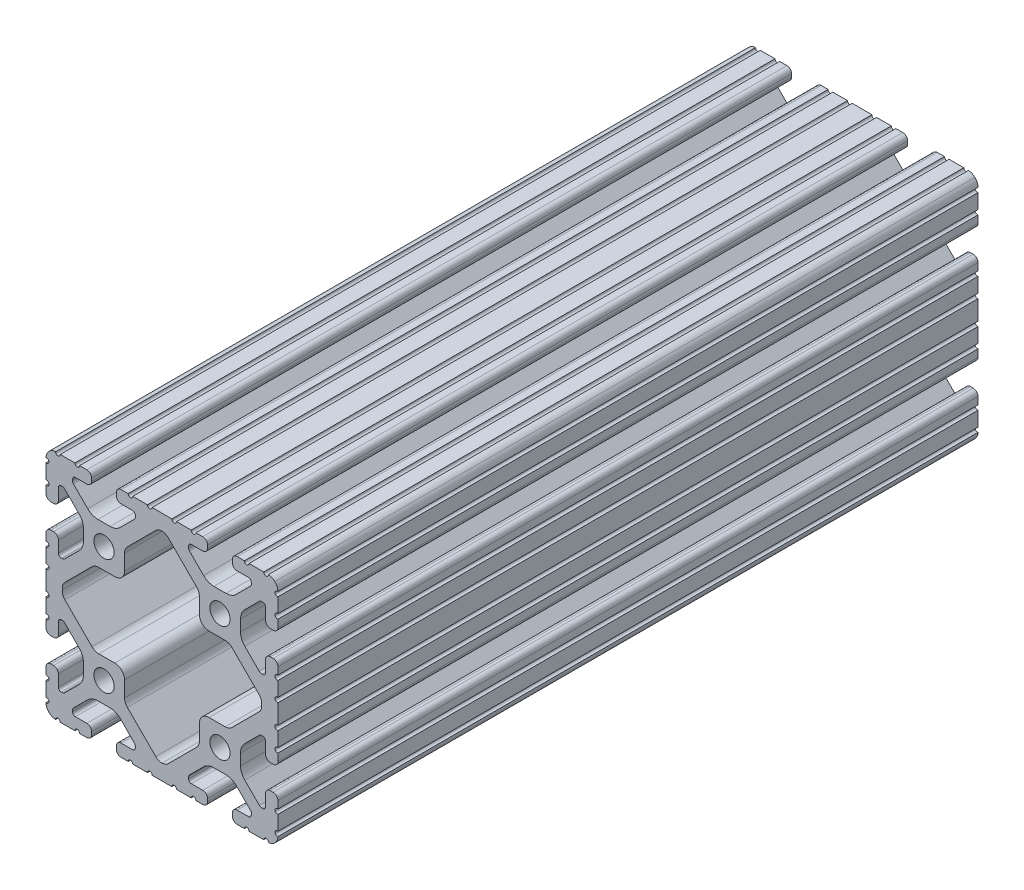
SolidWorks part; units mm, degrees
ref_plane "Front Plane" through (0, 0, 0) normal (0, 0, 1) x (1, 0, 0)
ref_plane "Top Plane" through (0, 0, 0) normal (0, 1, 0) x (1, 0, 0)
ref_plane "Right Plane" through (0, 0, 0) normal (1, 0, 0) x (0, 0, -1)
sketch "Sketch1" plane through (0, 0, 0) normal (0, 0, 1) x (1, 0, 0)
  line L0 (0, 38.1) -> (0, -38.1) construction
  line L1 (-38.1, -38.1) -> (38.1, -38.1) construction
  line L2 (-38.1, -38.1) -> (-38.1, 38.1) construction
  line L3 (-38.1, 38.1) -> (38.1, 38.1) construction
  line L4 (38.1, -38.1) -> (38.1, 38.1) construction
  line L5 (0, 38.1) -> (0, -38.1) construction
  line L6 (-38.1, 0) -> (38.1, 0) construction
  line L7 (-19.05, 19.05) -> (19.05, 19.05) construction
  line L8 (-19.05, 19.05) -> (-19.05, -19.05) construction
  line L9 (-19.05, -19.05) -> (19.05, -19.05) construction
  line L10 (19.05, 19.05) -> (19.05, -19.05) construction
  line L11 (-23.114, 38.1) -> (-23.114, -38.1) construction
  line L12 (-23.114, -38.1) -> (-14.986, 38.1) construction
  line L13 (-14.986, 38.1) -> (-14.986, -38.1) construction
  circle A0 centre (19.05, 19.05) radius 3.3274
  point P0 (0, 0)
  point P9 (0, 0)
  point P12 (-19.05, 0)
  line B0 (-11.3637, -22.8433) -> (-2.0515, -32.1555)
  line B1 (-12.2936, -15.4686) -> (-12.2936, -20.5983)
  line B2 (-20.769, -12.2936) -> (-15.4686, -12.2936)
  line B3 (-31.9021, -2.4756) -> (-23.0141, -11.3637)
  line B4 (-23.0141, 11.3637) -> (-31.9021, 2.4756)
  line B5 (-15.4686, 12.2936) -> (-20.769, 12.2936)
  line B6 (-12.2936, 20.5983) -> (-12.2936, 15.4686)
  line B7 (-2.0515, 32.1555) -> (-11.3637, 22.8433)
  line B8 (11.3637, 22.8433) -> (2.0515, 32.1555)
  line B9 (12.2936, 15.4686) -> (12.2936, 20.5983)
  line B10 (20.769, 12.2936) -> (15.4686, 12.2936)
  line B11 (31.9021, 2.4756) -> (23.0141, 11.3637)
  line B12 (23.0141, -11.3637) -> (31.9021, -2.4756)
  line B13 (15.4686, -12.2936) -> (20.769, -12.2936)
  line B14 (12.2936, -20.5983) -> (12.2936, -15.4686)
  line B15 (2.0515, -32.1555) -> (11.3637, -22.8433)
  line B16 (-4.7773, 38.1) -> (-9.6053, 38.1)
  line B17 (-11.1289, 38.1) -> (-13.4112, 38.1)
  line B18 (-14.986, 36.5252) -> (-14.986, 35.6108)
  line B19 (-13.4112, 34.036) -> (-9.652, 34.036)
  line B20 (-8.763, 33.147) -> (-8.763, 32.4935)
  line B21 (-9.0234, 31.8649) -> (-13.6907, 27.1976)
  line B22 (-17.0493, 25.8064) -> (-21.0507, 25.8064)
  line B23 (-24.4093, 27.1976) -> (-29.1002, 31.8885)
  line B24 (-29.337, 32.7207) -> (-29.337, 33.147)
  line B25 (-28.448, 34.036) -> (-24.6888, 34.036)
  line B26 (-23.114, 35.6108) -> (-23.114, 36.5252)
  line B27 (-24.6888, 38.1) -> (-27.0772, 38.1)
  line B28 (-28.6011, 38.1) -> (-33.4288, 38.1)
  line B29 (-38.1, 33.373) -> (-38.1, 28.5453)
  line B30 (-38.1, 27.0238) -> (-38.1, 24.6302)
  line B31 (-36.5252, 23.0554) -> (-35.6108, 23.0554)
  line B32 (-34.036, 24.6302) -> (-34.036, 28.448)
  line B33 (-33.147, 29.337) -> (-32.6643, 29.337)
  line B34 (-32.0357, 29.0766) -> (-27.1976, 24.2385)
  line B35 (-25.8064, 20.8799) -> (-25.8064, 17.2201)
  line B36 (-27.1976, 13.8615) -> (-31.9489, 9.1101)
  line B37 (-32.7869, 8.763) -> (-33.0603, 8.763)
  line B38 (-34.036, 9.7387) -> (-34.036, 13.4698)
  line B39 (-35.6108, 15.0446) -> (-36.5252, 15.0446)
  line B40 (-38.1, 13.4698) -> (-38.1, 11.075)
  line B41 (-38.1, 9.552) -> (-38.1, 4.7238)
  line B42 (-38.1, 3.2007) -> (-38.1, -3.2007)
  line B43 (-38.1, -4.7238) -> (-38.1, -9.552)
  line B44 (-38.1, -11.075) -> (-38.1, -13.4698)
  line B45 (-36.5252, -15.0446) -> (-35.6108, -15.0446)
  line B46 (-34.036, -13.4698) -> (-34.036, -9.7387)
  line B47 (-33.0603, -8.763) -> (-32.7869, -8.763)
  line B48 (-31.9489, -9.1101) -> (-27.1976, -13.8615)
  line B49 (-25.8064, -17.2201) -> (-25.8064, -20.8799)
  line B50 (-27.1976, -24.2385) -> (-32.0357, -29.0766)
  line B51 (-32.6643, -29.337) -> (-33.147, -29.337)
  line B52 (-34.036, -28.448) -> (-34.036, -24.6302)
  line B53 (-35.6108, -23.0554) -> (-36.5252, -23.0554)
  line B54 (-38.1, -24.6302) -> (-38.1, -27.0238)
  line B55 (-38.1, -28.5453) -> (-38.1, -33.373)
  line B56 (-33.4288, -38.1) -> (-28.6011, -38.1)
  line B57 (-27.0772, -38.1) -> (-24.6888, -38.1)
  line B58 (-23.114, -36.5252) -> (-23.114, -35.6108)
  line B59 (-24.6888, -34.036) -> (-28.448, -34.036)
  line B60 (-29.337, -33.147) -> (-29.337, -32.7207)
  line B61 (-29.1002, -31.8885) -> (-24.4093, -27.1976)
  line B62 (-21.0507, -25.8064) -> (-17.0493, -25.8064)
  line B63 (-13.6907, -27.1976) -> (-9.0234, -31.8649)
  line B64 (-8.763, -32.4935) -> (-8.763, -33.147)
  line B65 (-9.652, -34.036) -> (-13.4112, -34.036)
  line B66 (-14.986, -35.6108) -> (-14.986, -36.5252)
  line B67 (-13.4112, -38.1) -> (-11.1289, -38.1)
  line B68 (-9.6053, -38.1) -> (-4.7773, -38.1)
  line B69 (-3.2537, -38.1) -> (3.2537, -38.1)
  line B70 (4.7773, -38.1) -> (9.6053, -38.1)
  line B71 (11.1289, -38.1) -> (13.4112, -38.1)
  line B72 (14.986, -36.5252) -> (14.986, -35.6108)
  line B73 (13.4112, -34.036) -> (9.652, -34.036)
  line B74 (8.763, -33.147) -> (8.763, -32.4935)
  line B75 (9.0234, -31.8649) -> (13.6907, -27.1976)
  line B76 (17.0493, -25.8064) -> (21.0507, -25.8064)
  line B77 (24.4093, -27.1976) -> (29.1002, -31.8885)
  line B78 (29.337, -32.7207) -> (29.337, -33.147)
  line B79 (28.448, -34.036) -> (24.6888, -34.036)
  line B80 (23.114, -35.6108) -> (23.114, -36.5252)
  line B81 (24.6888, -38.1) -> (27.0772, -38.1)
  line B82 (28.6011, -38.1) -> (33.4288, -38.1)
  line B83 (38.1, -33.373) -> (38.1, -28.5453)
  line B84 (38.1, -27.0238) -> (38.1, -24.6302)
  line B85 (36.5252, -23.0554) -> (35.6108, -23.0554)
  line B86 (34.036, -24.6302) -> (34.036, -28.448)
  line B87 (33.147, -29.337) -> (32.6643, -29.337)
  line B88 (32.0357, -29.0766) -> (27.1976, -24.2385)
  line B89 (25.8064, -20.8799) -> (25.8064, -17.2201)
  line B90 (27.1976, -13.8615) -> (31.9489, -9.1101)
  line B91 (32.7869, -8.763) -> (33.0603, -8.763)
  line B92 (34.036, -9.7387) -> (34.036, -13.4698)
  line B93 (35.6108, -15.0446) -> (36.5252, -15.0446)
  line B94 (38.1, -13.4698) -> (38.1, -11.075)
  line B95 (38.1, -9.552) -> (38.1, -4.7238)
  line B96 (38.1, -3.2007) -> (38.1, 3.2007)
  line B97 (38.1, 4.7238) -> (38.1, 9.552)
  line B98 (38.1, 11.075) -> (38.1, 13.4698)
  line B99 (36.5252, 15.0446) -> (35.6108, 15.0446)
  line B100 (34.036, 13.4698) -> (34.036, 9.7387)
  line B101 (33.0603, 8.763) -> (32.7869, 8.763)
  line B102 (31.9489, 9.1101) -> (27.1976, 13.8615)
  line B103 (25.8064, 17.2201) -> (25.8064, 20.8799)
  line B104 (27.1976, 24.2385) -> (32.0357, 29.0766)
  line B105 (32.6643, 29.337) -> (33.147, 29.337)
  line B106 (34.036, 28.448) -> (34.036, 24.6302)
  line B107 (35.6108, 23.0554) -> (36.5252, 23.0554)
  line B108 (38.1, 24.6302) -> (38.1, 27.0238)
  line B109 (38.1, 28.5453) -> (38.1, 33.373)
  line B110 (33.4288, 38.1) -> (28.6011, 38.1)
  line B111 (27.0772, 38.1) -> (24.6888, 38.1)
  line B112 (23.114, 36.5252) -> (23.114, 35.6108)
  line B113 (24.6888, 34.036) -> (28.448, 34.036)
  line B114 (29.337, 33.147) -> (29.337, 32.7207)
  line B115 (29.1002, 31.8885) -> (24.4093, 27.1976)
  line B116 (21.0507, 25.8064) -> (17.0493, 25.8064)
  line B117 (13.6907, 27.1976) -> (9.0234, 31.8649)
  line B118 (8.763, 32.4935) -> (8.763, 33.147)
  line B119 (9.652, 34.036) -> (13.4112, 34.036)
  line B120 (14.986, 35.6108) -> (14.986, 36.5252)
  line B121 (13.4112, 38.1) -> (11.1289, 38.1)
  line B122 (9.6053, 38.1) -> (4.7773, 38.1)
  line B123 (3.2537, 38.1) -> (-3.2537, 38.1)
  circle B124 centre (-19.05, 19.05) radius 3.3274
  circle B125 centre (-19.05, -19.05) radius 3.3274
  circle B126 centre (19.05, -19.05) radius 3.3274
  circle B127 centre (19.05, 19.05) radius 3.3274
  arc B128 (0, -33.011) -> (2.0515, -32.1555) centre (-0.0139, -30.09) ccw
  arc B129 (-2.0515, -32.1555) -> (0, -33.011) centre (0.0139, -30.09) ccw
  arc B130 (-12.2936, -20.5983) -> (-11.3637, -22.8433) centre (-9.1186, -20.5983) ccw
  arc B131 (-12.2936, -15.4686) -> (-15.4686, -12.2936) centre (-15.4686, -15.4686) ccw
  arc B132 (-23.0141, -11.3637) -> (-20.769, -12.2936) centre (-20.769, -9.1186) ccw
  arc B133 (-32.7287, 0) -> (-31.9021, -2.4756) centre (-29.8367, -0.4102) ccw
  arc B134 (-31.9021, 2.4756) -> (-32.7287, 0) centre (-29.8367, 0.4102) ccw
  arc B135 (-20.769, 12.2936) -> (-23.0141, 11.3637) centre (-20.769, 9.1186) ccw
  arc B136 (-15.4686, 12.2936) -> (-12.2936, 15.4686) centre (-15.4686, 15.4686) ccw
  arc B137 (-11.3637, 22.8433) -> (-12.2936, 20.5983) centre (-9.1186, 20.5983) ccw
  arc B138 (0, 33.011) -> (-2.0515, 32.1555) centre (0.0139, 30.09) ccw
  arc B139 (2.0515, 32.1555) -> (0, 33.011) centre (-0.0139, 30.09) ccw
  arc B140 (12.2936, 20.5983) -> (11.3637, 22.8433) centre (9.1186, 20.5983) ccw
  arc B141 (12.2936, 15.4686) -> (15.4686, 12.2936) centre (15.4686, 15.4686) ccw
  arc B142 (23.0141, 11.3637) -> (20.769, 12.2936) centre (20.769, 9.1186) ccw
  arc B143 (32.7287, 0) -> (31.9021, 2.4756) centre (29.8367, 0.4102) ccw
  arc B144 (31.9021, -2.4756) -> (32.7287, 0) centre (29.8367, -0.4102) ccw
  arc B145 (20.769, -12.2936) -> (23.0141, -11.3637) centre (20.769, -9.1186) ccw
  arc B146 (15.4686, -12.2936) -> (12.2936, -15.4686) centre (15.4686, -15.4686) ccw
  arc B147 (11.3637, -22.8433) -> (12.2936, -20.5983) centre (9.1186, -20.5983) ccw
  arc B148 (-4.7773, 38.1) -> (-3.2537, 38.1) centre (-4.0155, 38.0824) ccw
  arc B149 (-11.1289, 38.1) -> (-9.6053, 38.1) centre (-10.3671, 38.0824) ccw
  arc B150 (-13.4112, 38.1) -> (-14.986, 36.5252) centre (-13.4112, 36.5252) ccw
  arc B151 (-14.986, 35.6108) -> (-13.4112, 34.036) centre (-13.4112, 35.6108) ccw
  arc B152 (-8.763, 33.147) -> (-9.652, 34.036) centre (-9.652, 33.147) ccw
  arc B153 (-9.0234, 31.8649) -> (-8.763, 32.4935) centre (-9.652, 32.4935) ccw
  arc B154 (-17.0493, 25.8064) -> (-13.6907, 27.1976) centre (-17.0493, 30.5562) ccw
  arc B155 (-24.4093, 27.1976) -> (-21.0507, 25.8064) centre (-21.0507, 30.5562) ccw
  arc B156 (-29.337, 32.7207) -> (-29.1002, 31.8885) centre (-28.4716, 32.5172) ccw
  arc B157 (-28.448, 34.036) -> (-29.337, 33.147) centre (-28.448, 33.147) ccw
  arc B158 (-24.6888, 34.036) -> (-23.114, 35.6108) centre (-24.6888, 35.6108) ccw
  arc B159 (-23.114, 36.5252) -> (-24.6888, 38.1) centre (-24.6888, 36.5252) ccw
  arc B160 (-28.6011, 38.1) -> (-27.0772, 38.1) centre (-27.8392, 38.0824) ccw
  arc B161 (-34.9527, 38.1) -> (-33.4288, 38.1) centre (-34.1907, 38.0824) ccw
  arc B162 (-34.9527, 38.1) -> (-37.0861, 37.1826) centre (-34.8521, 34.9266) ccw
  arc B163 (-37.0861, 37.1826) -> (-38.1, 34.8455) centre (-34.925, 34.8566) ccw
  arc B164 (-38.1, 33.373) -> (-38.1, 34.8455) centre (-37.9035, 34.1092) ccw
  arc B165 (-38.1, 27.0238) -> (-38.1, 28.5453) centre (-37.9035, 27.7845) ccw
  arc B166 (-38.1, 24.6302) -> (-36.5252, 23.0554) centre (-36.5252, 24.6302) ccw
  arc B167 (-35.6108, 23.0554) -> (-34.036, 24.6302) centre (-35.6108, 24.6302) ccw
  arc B168 (-33.147, 29.337) -> (-34.036, 28.448) centre (-33.147, 28.448) ccw
  arc B169 (-32.0357, 29.0766) -> (-32.6643, 29.337) centre (-32.6643, 28.448) ccw
  arc B170 (-25.8064, 20.8799) -> (-27.1976, 24.2385) centre (-30.5562, 20.8799) ccw
  arc B171 (-27.1976, 13.8615) -> (-25.8064, 17.2201) centre (-30.5562, 17.2201) ccw
  arc B172 (-32.7869, 8.763) -> (-31.9489, 9.1101) centre (-32.7869, 9.9481) ccw
  arc B173 (-34.036, 9.7387) -> (-33.0603, 8.763) centre (-33.0603, 9.7387) ccw
  arc B174 (-34.036, 13.4698) -> (-35.6108, 15.0446) centre (-35.6108, 13.4698) ccw
  arc B175 (-36.5252, 15.0446) -> (-38.1, 13.4698) centre (-36.5252, 13.4698) ccw
  arc B176 (-38.1, 9.552) -> (-38.1, 11.075) centre (-37.9035, 10.3135) ccw
  arc B177 (-38.1, 3.2007) -> (-38.1, 4.7238) centre (-37.9035, 3.9622) ccw
  arc B178 (-38.1, -4.7238) -> (-38.1, -3.2007) centre (-37.9035, -3.9622) ccw
  arc B179 (-38.1, -11.075) -> (-38.1, -9.552) centre (-37.9035, -10.3135) ccw
  arc B180 (-38.1, -13.4698) -> (-36.5252, -15.0446) centre (-36.5252, -13.4698) ccw
  arc B181 (-35.6108, -15.0446) -> (-34.036, -13.4698) centre (-35.6108, -13.4698) ccw
  arc B182 (-33.0603, -8.763) -> (-34.036, -9.7387) centre (-33.0603, -9.7387) ccw
  arc B183 (-31.9489, -9.1101) -> (-32.7869, -8.763) centre (-32.7869, -9.9481) ccw
  arc B184 (-25.8064, -17.2201) -> (-27.1976, -13.8615) centre (-30.5562, -17.2201) ccw
  arc B185 (-27.1976, -24.2385) -> (-25.8064, -20.8799) centre (-30.5562, -20.8799) ccw
  arc B186 (-32.6643, -29.337) -> (-32.0357, -29.0766) centre (-32.6643, -28.448) ccw
  arc B187 (-34.036, -28.448) -> (-33.147, -29.337) centre (-33.147, -28.448) ccw
  arc B188 (-34.036, -24.6302) -> (-35.6108, -23.0554) centre (-35.6108, -24.6302) ccw
  arc B189 (-36.5252, -23.0554) -> (-38.1, -24.6302) centre (-36.5252, -24.6302) ccw
  arc B190 (-38.1, -28.5453) -> (-38.1, -27.0238) centre (-37.9035, -27.7845) ccw
  arc B191 (-38.1, -34.8455) -> (-38.1, -33.373) centre (-37.9035, -34.1092) ccw
  arc B192 (-38.1, -34.8455) -> (-37.0861, -37.1826) centre (-34.925, -34.8566) ccw
  arc B193 (-37.0861, -37.1826) -> (-34.9527, -38.1) centre (-34.8521, -34.9266) ccw
  arc B194 (-33.4288, -38.1) -> (-34.9527, -38.1) centre (-34.1907, -38.0824) ccw
  arc B195 (-27.0772, -38.1) -> (-28.6011, -38.1) centre (-27.8392, -38.0824) ccw
  arc B196 (-24.6888, -38.1) -> (-23.114, -36.5252) centre (-24.6888, -36.5252) ccw
  arc B197 (-23.114, -35.6108) -> (-24.6888, -34.036) centre (-24.6888, -35.6108) ccw
  arc B198 (-29.337, -33.147) -> (-28.448, -34.036) centre (-28.448, -33.147) ccw
  arc B199 (-29.1002, -31.8885) -> (-29.337, -32.7207) centre (-28.4716, -32.5172) ccw
  arc B200 (-21.0507, -25.8064) -> (-24.4093, -27.1976) centre (-21.0507, -30.5562) ccw
  arc B201 (-13.6907, -27.1976) -> (-17.0493, -25.8064) centre (-17.0493, -30.5562) ccw
  arc B202 (-8.763, -32.4935) -> (-9.0234, -31.8649) centre (-9.652, -32.4935) ccw
  arc B203 (-9.652, -34.036) -> (-8.763, -33.147) centre (-9.652, -33.147) ccw
  arc B204 (-13.4112, -34.036) -> (-14.986, -35.6108) centre (-13.4112, -35.6108) ccw
  arc B205 (-14.986, -36.5252) -> (-13.4112, -38.1) centre (-13.4112, -36.5252) ccw
  arc B206 (-9.6053, -38.1) -> (-11.1289, -38.1) centre (-10.3671, -38.0824) ccw
  arc B207 (-3.2537, -38.1) -> (-4.7773, -38.1) centre (-4.0155, -38.0824) ccw
  arc B208 (4.7773, -38.1) -> (3.2537, -38.1) centre (4.0155, -38.0824) ccw
  arc B209 (11.1289, -38.1) -> (9.6053, -38.1) centre (10.3671, -38.0824) ccw
  arc B210 (13.4112, -38.1) -> (14.986, -36.5252) centre (13.4112, -36.5252) ccw
  arc B211 (14.986, -35.6108) -> (13.4112, -34.036) centre (13.4112, -35.6108) ccw
  arc B212 (8.763, -33.147) -> (9.652, -34.036) centre (9.652, -33.147) ccw
  arc B213 (9.0234, -31.8649) -> (8.763, -32.4935) centre (9.652, -32.4935) ccw
  arc B214 (17.0493, -25.8064) -> (13.6907, -27.1976) centre (17.0493, -30.5562) ccw
  arc B215 (24.4093, -27.1976) -> (21.0507, -25.8064) centre (21.0507, -30.5562) ccw
  arc B216 (29.337, -32.7207) -> (29.1002, -31.8885) centre (28.4716, -32.5172) ccw
  arc B217 (28.448, -34.036) -> (29.337, -33.147) centre (28.448, -33.147) ccw
  arc B218 (24.6888, -34.036) -> (23.114, -35.6108) centre (24.6888, -35.6108) ccw
  arc B219 (23.114, -36.5252) -> (24.6888, -38.1) centre (24.6888, -36.5252) ccw
  arc B220 (28.6011, -38.1) -> (27.0772, -38.1) centre (27.8392, -38.0824) ccw
  arc B221 (34.9527, -38.1) -> (33.4288, -38.1) centre (34.1907, -38.0824) ccw
  arc B222 (34.9527, -38.1) -> (37.0861, -37.1826) centre (34.8521, -34.9266) ccw
  arc B223 (37.0861, -37.1826) -> (38.1, -34.8455) centre (34.925, -34.8566) ccw
  arc B224 (38.1, -33.373) -> (38.1, -34.8455) centre (37.9035, -34.1092) ccw
  arc B225 (38.1, -27.0238) -> (38.1, -28.5453) centre (37.9035, -27.7845) ccw
  arc B226 (38.1, -24.6302) -> (36.5252, -23.0554) centre (36.5252, -24.6302) ccw
  arc B227 (35.6108, -23.0554) -> (34.036, -24.6302) centre (35.6108, -24.6302) ccw
  arc B228 (33.147, -29.337) -> (34.036, -28.448) centre (33.147, -28.448) ccw
  arc B229 (32.0357, -29.0766) -> (32.6643, -29.337) centre (32.6643, -28.448) ccw
  arc B230 (25.8064, -20.8799) -> (27.1976, -24.2385) centre (30.5562, -20.8799) ccw
  arc B231 (27.1976, -13.8615) -> (25.8064, -17.2201) centre (30.5562, -17.2201) ccw
  arc B232 (32.7869, -8.763) -> (31.9489, -9.1101) centre (32.7869, -9.9481) ccw
  arc B233 (34.036, -9.7387) -> (33.0603, -8.763) centre (33.0603, -9.7387) ccw
  arc B234 (34.036, -13.4698) -> (35.6108, -15.0446) centre (35.6108, -13.4698) ccw
  arc B235 (36.5252, -15.0446) -> (38.1, -13.4698) centre (36.5252, -13.4698) ccw
  arc B236 (38.1, -9.552) -> (38.1, -11.075) centre (37.9035, -10.3135) ccw
  arc B237 (38.1, -3.2007) -> (38.1, -4.7238) centre (37.9035, -3.9622) ccw
  arc B238 (38.1, 4.7238) -> (38.1, 3.2007) centre (37.9035, 3.9622) ccw
  arc B239 (38.1, 11.075) -> (38.1, 9.552) centre (37.9035, 10.3135) ccw
  arc B240 (38.1, 13.4698) -> (36.5252, 15.0446) centre (36.5252, 13.4698) ccw
  arc B241 (35.6108, 15.0446) -> (34.036, 13.4698) centre (35.6108, 13.4698) ccw
  arc B242 (33.0603, 8.763) -> (34.036, 9.7387) centre (33.0603, 9.7387) ccw
  arc B243 (31.9489, 9.1101) -> (32.7869, 8.763) centre (32.7869, 9.9481) ccw
  arc B244 (25.8064, 17.2201) -> (27.1976, 13.8615) centre (30.5562, 17.2201) ccw
  arc B245 (27.1976, 24.2385) -> (25.8064, 20.8799) centre (30.5562, 20.8799) ccw
  arc B246 (32.6643, 29.337) -> (32.0357, 29.0766) centre (32.6643, 28.448) ccw
  arc B247 (34.036, 28.448) -> (33.147, 29.337) centre (33.147, 28.448) ccw
  arc B248 (34.036, 24.6302) -> (35.6108, 23.0554) centre (35.6108, 24.6302) ccw
  arc B249 (36.5252, 23.0554) -> (38.1, 24.6302) centre (36.5252, 24.6302) ccw
  arc B250 (38.1, 28.5453) -> (38.1, 27.0238) centre (37.9035, 27.7845) ccw
  arc B251 (38.1, 34.8455) -> (38.1, 33.373) centre (37.9035, 34.1092) ccw
  arc B252 (38.1, 34.8455) -> (37.0861, 37.1826) centre (34.925, 34.8566) ccw
  arc B253 (37.0861, 37.1826) -> (34.9527, 38.1) centre (34.8521, 34.9266) ccw
  arc B254 (33.4288, 38.1) -> (34.9527, 38.1) centre (34.1907, 38.0824) ccw
  arc B255 (27.0772, 38.1) -> (28.6011, 38.1) centre (27.8392, 38.0824) ccw
  arc B256 (24.6888, 38.1) -> (23.114, 36.5252) centre (24.6888, 36.5252) ccw
  arc B257 (23.114, 35.6108) -> (24.6888, 34.036) centre (24.6888, 35.6108) ccw
  arc B258 (29.337, 33.147) -> (28.448, 34.036) centre (28.448, 33.147) ccw
  arc B259 (29.1002, 31.8885) -> (29.337, 32.7207) centre (28.4716, 32.5172) ccw
  arc B260 (21.0507, 25.8064) -> (24.4093, 27.1976) centre (21.0507, 30.5562) ccw
  arc B261 (13.6907, 27.1976) -> (17.0493, 25.8064) centre (17.0493, 30.5562) ccw
  arc B262 (8.763, 32.4935) -> (9.0234, 31.8649) centre (9.652, 32.4935) ccw
  arc B263 (9.652, 34.036) -> (8.763, 33.147) centre (9.652, 33.147) ccw
  arc B264 (13.4112, 34.036) -> (14.986, 35.6108) centre (13.4112, 35.6108) ccw
  arc B265 (14.986, 36.5252) -> (13.4112, 38.1) centre (13.4112, 36.5252) ccw
  arc B266 (9.6053, 38.1) -> (11.1289, 38.1) centre (10.3671, 38.0824) ccw
  arc B267 (3.2537, 38.1) -> (4.7773, 38.1) centre (4.0155, 38.0824) ccw
  dimension "Center Hole Diameter" = 6.6548
  dimension "Rail Width" = 76.2
  dimension "Rail Height" = 76.2
  dimension "T-Slot Width" = 8.128
sketch_block_instance "Block1-1"
sketch_block "Block1"
sketch "Sketch2" plane through (0, 0, 0) normal (1, 0, 0) x (0, 0, -1)
  line L0 (-115, 0) -> (115, 0) construction
  line L1 (-115, 38.1) -> (-115, -38.1) construction
  line L2 (-115, -38.1) -> (115, -38.1) construction
  line L3 (115, -38.1) -> (115, 38.1) construction
  line L4 (-13.4, 0) -> (-13.4, 38.1) construction
  line L5 (-13.4, 38.1) -> (13.4, 38.1) construction
  line L6 (13.4, 38.1) -> (13.4, 0) construction
  point P5 (13.4, 0)
  point P10 (-13.4, 0)
  dimension "D1" = 101.6
  dimension "Length" = 230
  dimension "D2" = 101.6
sketch "Sketch3" plane through (0, 0, 0) normal (0, 0, 1) x (1, 0, 0)
  line L0 (-11.3637, -22.8433) -> (-2.0515, -32.1555) construction
  line L1 (-12.2936, -15.4686) -> (-12.2936, -20.5983) construction
  line L2 (-20.769, -12.2936) -> (-15.4686, -12.2936) construction
  line L3 (-31.9021, -2.4756) -> (-23.0141, -11.3637) construction
  line L4 (-23.0141, 11.3637) -> (-31.9021, 2.4756) construction
  line L5 (-15.4686, 12.2936) -> (-20.769, 12.2936) construction
  line L6 (-12.2936, 20.5983) -> (-12.2936, 15.4686) construction
  line L7 (-2.0515, 32.1555) -> (-11.3637, 22.8433) construction
  line L8 (11.3637, 22.8433) -> (2.0515, 32.1555) construction
  line L9 (12.2936, 15.4686) -> (12.2936, 20.5983) construction
  line L10 (20.769, 12.2936) -> (15.4686, 12.2936) construction
  line L11 (31.9021, 2.4756) -> (23.0141, 11.3637) construction
  line L12 (23.0141, -11.3637) -> (31.9021, -2.4756) construction
  line L13 (15.4686, -12.2936) -> (20.769, -12.2936) construction
  line L14 (12.2936, -20.5983) -> (12.2936, -15.4686) construction
  line L15 (2.0515, -32.1555) -> (11.3637, -22.8433) construction
  line L16 (34.036, 28.448) -> (34.036, 24.6302) construction
  line L17 (35.6108, 23.0554) -> (36.5252, 23.0554) construction
  line L18 (38.1, 24.6302) -> (38.1, 27.0238) construction
  line L19 (38.1, 28.5453) -> (38.1, 33.373) construction
  line L20 (33.4288, 38.1) -> (28.6011, 38.1) construction
  line L21 (27.0772, 38.1) -> (24.6888, 38.1) construction
  line L22 (23.114, 36.5252) -> (23.114, 35.6108) construction
  line L23 (24.6888, 34.036) -> (28.448, 34.036) construction
  line L24 (29.337, 33.147) -> (29.337, 32.7207) construction
  line L25 (29.1002, 31.8885) -> (24.4093, 27.1976) construction
  line L26 (21.0507, 25.8064) -> (17.0493, 25.8064) construction
  line L27 (13.6907, 27.1976) -> (9.0234, 31.8649) construction
  line L28 (8.763, 32.4935) -> (8.763, 33.147) construction
  line L29 (9.652, 34.036) -> (13.4112, 34.036) construction
  line L30 (14.986, 35.6108) -> (14.986, 36.5252) construction
  line L31 (13.4112, 38.1) -> (11.1289, 38.1) construction
  line L32 (9.6053, 38.1) -> (4.7773, 38.1) construction
  line L33 (3.2537, 38.1) -> (-3.2537, 38.1) construction
  line L34 (-4.7773, 38.1) -> (-9.6053, 38.1) construction
  line L35 (-11.1289, 38.1) -> (-13.4112, 38.1) construction
  line L36 (-14.986, 36.5252) -> (-14.986, 35.6108) construction
  line L37 (-13.4112, 34.036) -> (-9.652, 34.036) construction
  line L38 (-8.763, 33.147) -> (-8.763, 32.4935) construction
  line L39 (-9.0234, 31.8649) -> (-13.6907, 27.1976) construction
  line L40 (-17.0493, 25.8064) -> (-21.0507, 25.8064) construction
  line L41 (-24.4093, 27.1976) -> (-29.1002, 31.8885) construction
  line L42 (-29.337, 32.7207) -> (-29.337, 33.147) construction
  line L43 (-28.448, 34.036) -> (-24.6888, 34.036) construction
  line L44 (-23.114, 35.6108) -> (-23.114, 36.5252) construction
  line L45 (-24.6888, 38.1) -> (-27.0772, 38.1) construction
  line L46 (-28.6011, 38.1) -> (-33.4288, 38.1) construction
  line L47 (-38.1, 33.373) -> (-38.1, 28.5453) construction
  line L48 (-38.1, 27.0238) -> (-38.1, 24.6302) construction
  line L49 (-36.5252, 23.0554) -> (-35.6108, 23.0554) construction
  line L50 (-34.036, 24.6302) -> (-34.036, 28.448) construction
  line L51 (-33.147, 29.337) -> (-32.6643, 29.337) construction
  line L52 (-32.0357, 29.0766) -> (-27.1976, 24.2385) construction
  line L53 (-25.8064, 20.8799) -> (-25.8064, 17.2201) construction
  line L54 (-27.1976, 13.8615) -> (-31.9489, 9.1101) construction
  line L55 (-32.7869, 8.763) -> (-33.0603, 8.763) construction
  line L56 (-34.036, 9.7387) -> (-34.036, 13.4698) construction
  line L57 (-35.6108, 15.0446) -> (-36.5252, 15.0446) construction
  line L58 (-38.1, 13.4698) -> (-38.1, 11.075) construction
  line L59 (-38.1, 9.552) -> (-38.1, 4.7238) construction
  line L60 (-38.1, 3.2007) -> (-38.1, -3.2007) construction
  line L61 (-38.1, -4.7238) -> (-38.1, -9.552) construction
  line L62 (-38.1, -11.075) -> (-38.1, -13.4698) construction
  line L63 (-36.5252, -15.0446) -> (-35.6108, -15.0446) construction
  line L64 (-34.036, -13.4698) -> (-34.036, -9.7387) construction
  line L65 (-33.0603, -8.763) -> (-32.7869, -8.763) construction
  line L66 (-31.9489, -9.1101) -> (-27.1976, -13.8615) construction
  line L67 (-25.8064, -17.2201) -> (-25.8064, -20.8799) construction
  line L68 (-27.1976, -24.2385) -> (-32.0357, -29.0766) construction
  line L69 (-32.6643, -29.337) -> (-33.147, -29.337) construction
  line L70 (-34.036, -28.448) -> (-34.036, -24.6302) construction
  line L71 (-35.6108, -23.0554) -> (-36.5252, -23.0554) construction
  line L72 (-38.1, -24.6302) -> (-38.1, -27.0238) construction
  line L73 (-38.1, -28.5453) -> (-38.1, -33.373) construction
  line L74 (-33.4288, -38.1) -> (-28.6011, -38.1) construction
  line L75 (-27.0772, -38.1) -> (-24.6888, -38.1) construction
  line L76 (-23.114, -36.5252) -> (-23.114, -35.6108) construction
  line L77 (-24.6888, -34.036) -> (-28.448, -34.036) construction
  line L78 (-29.337, -33.147) -> (-29.337, -32.7207) construction
  line L79 (-29.1002, -31.8885) -> (-24.4093, -27.1976) construction
  line L80 (-21.0507, -25.8064) -> (-17.0493, -25.8064) construction
  line L81 (-13.6907, -27.1976) -> (-9.0234, -31.8649) construction
  line L82 (-8.763, -32.4935) -> (-8.763, -33.147) construction
  line L83 (-9.652, -34.036) -> (-13.4112, -34.036) construction
  line L84 (-14.986, -35.6108) -> (-14.986, -36.5252) construction
  line L85 (-13.4112, -38.1) -> (-11.1289, -38.1) construction
  line L86 (-9.6053, -38.1) -> (-4.7773, -38.1) construction
  line L87 (-3.2537, -38.1) -> (3.2537, -38.1) construction
  line L88 (4.7773, -38.1) -> (9.6053, -38.1) construction
  line L89 (11.1289, -38.1) -> (13.4112, -38.1) construction
  line L90 (14.986, -36.5252) -> (14.986, -35.6108) construction
  line L91 (13.4112, -34.036) -> (9.652, -34.036) construction
  line L92 (8.763, -33.147) -> (8.763, -32.4935) construction
  line L93 (9.0234, -31.8649) -> (13.6907, -27.1976) construction
  line L94 (17.0493, -25.8064) -> (21.0507, -25.8064) construction
  line L95 (24.4093, -27.1976) -> (29.1002, -31.8885) construction
  line L96 (29.337, -32.7207) -> (29.337, -33.147) construction
  line L97 (28.448, -34.036) -> (24.6888, -34.036) construction
  line L98 (23.114, -35.6108) -> (23.114, -36.5252) construction
  line L99 (24.6888, -38.1) -> (27.0772, -38.1) construction
  line L100 (28.6011, -38.1) -> (33.4288, -38.1) construction
  line L101 (38.1, -33.373) -> (38.1, -28.5453) construction
  line L102 (38.1, -27.0238) -> (38.1, -24.6302) construction
  line L103 (36.5252, -23.0554) -> (35.6108, -23.0554) construction
  line L104 (34.036, -24.6302) -> (34.036, -28.448) construction
  line L105 (33.147, -29.337) -> (32.6643, -29.337) construction
  line L106 (32.0357, -29.0766) -> (27.1976, -24.2385) construction
  line L107 (25.8064, -20.8799) -> (25.8064, -17.2201) construction
  line L108 (27.1976, -13.8615) -> (31.9489, -9.1101) construction
  line L109 (32.7869, -8.763) -> (33.0603, -8.763) construction
  line L110 (34.036, -9.7387) -> (34.036, -13.4698) construction
  line L111 (35.6108, -15.0446) -> (36.5252, -15.0446) construction
  line L112 (38.1, -13.4698) -> (38.1, -11.075) construction
  line L113 (38.1, -9.552) -> (38.1, -4.7238) construction
  line L114 (38.1, -3.2007) -> (38.1, 3.2007) construction
  line L115 (38.1, 4.7238) -> (38.1, 9.552) construction
  line L116 (38.1, 11.075) -> (38.1, 13.4698) construction
  line L117 (36.5252, 15.0446) -> (35.6108, 15.0446) construction
  line L118 (34.036, 13.4698) -> (34.036, 9.7387) construction
  line L119 (33.0603, 8.763) -> (32.7869, 8.763) construction
  line L120 (31.9489, 9.1101) -> (27.1976, 13.8615) construction
  line L121 (25.8064, 17.2201) -> (25.8064, 20.8799) construction
  line L122 (27.1976, 24.2385) -> (32.0357, 29.0766) construction
  line L123 (32.6643, 29.337) -> (33.147, 29.337) construction
  line L124 (-11.3637, -22.8433) -> (-2.0515, -32.1555)
  line L125 (-12.2936, -15.4686) -> (-12.2936, -20.5983)
  line L126 (-20.769, -12.2936) -> (-15.4686, -12.2936)
  line L127 (-31.9021, -2.4756) -> (-23.0141, -11.3637)
  line L128 (-23.0141, 11.3637) -> (-31.9021, 2.4756)
  line L129 (-15.4686, 12.2936) -> (-20.769, 12.2936)
  line L130 (-12.2936, 20.5983) -> (-12.2936, 15.4686)
  line L131 (-2.0515, 32.1555) -> (-11.3637, 22.8433)
  line L132 (11.3637, 22.8433) -> (2.0515, 32.1555)
  line L133 (12.2936, 15.4686) -> (12.2936, 20.5983)
  line L134 (20.769, 12.2936) -> (15.4686, 12.2936)
  line L135 (31.9021, 2.4756) -> (23.0141, 11.3637)
  line L136 (23.0141, -11.3637) -> (31.9021, -2.4756)
  line L137 (15.4686, -12.2936) -> (20.769, -12.2936)
  line L138 (12.2936, -20.5983) -> (12.2936, -15.4686)
  line L139 (2.0515, -32.1555) -> (11.3637, -22.8433)
  line L140 (34.036, 28.448) -> (34.036, 24.6302)
  line L141 (35.6108, 23.0554) -> (36.5252, 23.0554)
  line L142 (38.1, 24.6302) -> (38.1, 27.0238)
  line L143 (38.1, 28.5453) -> (38.1, 33.373)
  line L144 (33.4288, 38.1) -> (28.6011, 38.1)
  line L145 (27.0772, 38.1) -> (24.6888, 38.1)
  line L146 (23.114, 36.5252) -> (23.114, 35.6108)
  line L147 (24.6888, 34.036) -> (28.448, 34.036)
  line L148 (29.337, 33.147) -> (29.337, 32.7207)
  line L149 (29.1002, 31.8885) -> (24.4093, 27.1976)
  line L150 (21.0507, 25.8064) -> (17.0493, 25.8064)
  line L151 (13.6907, 27.1976) -> (9.0234, 31.8649)
  line L152 (8.763, 32.4935) -> (8.763, 33.147)
  line L153 (9.652, 34.036) -> (13.4112, 34.036)
  line L154 (14.986, 35.6108) -> (14.986, 36.5252)
  line L155 (13.4112, 38.1) -> (11.1289, 38.1)
  line L156 (9.6053, 38.1) -> (4.7773, 38.1)
  line L157 (3.2537, 38.1) -> (-3.2537, 38.1)
  line L158 (-4.7773, 38.1) -> (-9.6053, 38.1)
  line L159 (-11.1289, 38.1) -> (-13.4112, 38.1)
  line L160 (-14.986, 36.5252) -> (-14.986, 35.6108)
  line L161 (-13.4112, 34.036) -> (-9.652, 34.036)
  line L162 (-8.763, 33.147) -> (-8.763, 32.4935)
  line L163 (-9.0234, 31.8649) -> (-13.6907, 27.1976)
  line L164 (-17.0493, 25.8064) -> (-21.0507, 25.8064)
  line L165 (-24.4093, 27.1976) -> (-29.1002, 31.8885)
  line L166 (-29.337, 32.7207) -> (-29.337, 33.147)
  line L167 (-28.448, 34.036) -> (-24.6888, 34.036)
  line L168 (-23.114, 35.6108) -> (-23.114, 36.5252)
  line L169 (-24.6888, 38.1) -> (-27.0772, 38.1)
  line L170 (-28.6011, 38.1) -> (-33.4288, 38.1)
  line L171 (-38.1, 33.373) -> (-38.1, 28.5453)
  line L172 (-38.1, 27.0238) -> (-38.1, 24.6302)
  line L173 (-36.5252, 23.0554) -> (-35.6108, 23.0554)
  line L174 (-34.036, 24.6302) -> (-34.036, 28.448)
  line L175 (-33.147, 29.337) -> (-32.6643, 29.337)
  line L176 (-32.0357, 29.0766) -> (-27.1976, 24.2385)
  line L177 (-25.8064, 20.8799) -> (-25.8064, 17.2201)
  line L178 (-27.1976, 13.8615) -> (-31.9489, 9.1101)
  line L179 (-32.7869, 8.763) -> (-33.0603, 8.763)
  line L180 (-34.036, 9.7387) -> (-34.036, 13.4698)
  line L181 (-35.6108, 15.0446) -> (-36.5252, 15.0446)
  line L182 (-38.1, 13.4698) -> (-38.1, 11.075)
  line L183 (-38.1, 9.552) -> (-38.1, 4.7238)
  line L184 (-38.1, 3.2007) -> (-38.1, -3.2007)
  line L185 (-38.1, -4.7238) -> (-38.1, -9.552)
  line L186 (-38.1, -11.075) -> (-38.1, -13.4698)
  line L187 (-36.5252, -15.0446) -> (-35.6108, -15.0446)
  line L188 (-34.036, -13.4698) -> (-34.036, -9.7387)
  line L189 (-33.0603, -8.763) -> (-32.7869, -8.763)
  line L190 (-31.9489, -9.1101) -> (-27.1976, -13.8615)
  line L191 (-25.8064, -17.2201) -> (-25.8064, -20.8799)
  line L192 (-27.1976, -24.2385) -> (-32.0357, -29.0766)
  line L193 (-32.6643, -29.337) -> (-33.147, -29.337)
  line L194 (-34.036, -28.448) -> (-34.036, -24.6302)
  line L195 (-35.6108, -23.0554) -> (-36.5252, -23.0554)
  line L196 (-38.1, -24.6302) -> (-38.1, -27.0238)
  line L197 (-38.1, -28.5453) -> (-38.1, -33.373)
  line L198 (-33.4288, -38.1) -> (-28.6011, -38.1)
  line L199 (-27.0772, -38.1) -> (-24.6888, -38.1)
  line L200 (-23.114, -36.5252) -> (-23.114, -35.6108)
  line L201 (-24.6888, -34.036) -> (-28.448, -34.036)
  line L202 (-29.337, -33.147) -> (-29.337, -32.7207)
  line L203 (-29.1002, -31.8885) -> (-24.4093, -27.1976)
  line L204 (-21.0507, -25.8064) -> (-17.0493, -25.8064)
  line L205 (-13.6907, -27.1976) -> (-9.0234, -31.8649)
  line L206 (-8.763, -32.4935) -> (-8.763, -33.147)
  line L207 (-9.652, -34.036) -> (-13.4112, -34.036)
  line L208 (-14.986, -35.6108) -> (-14.986, -36.5252)
  line L209 (-13.4112, -38.1) -> (-11.1289, -38.1)
  line L210 (-9.6053, -38.1) -> (-4.7773, -38.1)
  line L211 (-3.2537, -38.1) -> (3.2537, -38.1)
  line L212 (4.7773, -38.1) -> (9.6053, -38.1)
  line L213 (11.1289, -38.1) -> (13.4112, -38.1)
  line L214 (14.986, -36.5252) -> (14.986, -35.6108)
  line L215 (13.4112, -34.036) -> (9.652, -34.036)
  line L216 (8.763, -33.147) -> (8.763, -32.4935)
  line L217 (9.0234, -31.8649) -> (13.6907, -27.1976)
  line L218 (17.0493, -25.8064) -> (21.0507, -25.8064)
  line L219 (24.4093, -27.1976) -> (29.1002, -31.8885)
  line L220 (29.337, -32.7207) -> (29.337, -33.147)
  line L221 (28.448, -34.036) -> (24.6888, -34.036)
  line L222 (23.114, -35.6108) -> (23.114, -36.5252)
  line L223 (24.6888, -38.1) -> (27.0772, -38.1)
  line L224 (28.6011, -38.1) -> (33.4288, -38.1)
  line L225 (38.1, -33.373) -> (38.1, -28.5453)
  line L226 (38.1, -27.0238) -> (38.1, -24.6302)
  line L227 (36.5252, -23.0554) -> (35.6108, -23.0554)
  line L228 (34.036, -24.6302) -> (34.036, -28.448)
  line L229 (33.147, -29.337) -> (32.6643, -29.337)
  line L230 (32.0357, -29.0766) -> (27.1976, -24.2385)
  line L231 (25.8064, -20.8799) -> (25.8064, -17.2201)
  line L232 (27.1976, -13.8615) -> (31.9489, -9.1101)
  line L233 (32.7869, -8.763) -> (33.0603, -8.763)
  line L234 (34.036, -9.7387) -> (34.036, -13.4698)
  line L235 (35.6108, -15.0446) -> (36.5252, -15.0446)
  line L236 (38.1, -13.4698) -> (38.1, -11.075)
  line L237 (38.1, -9.552) -> (38.1, -4.7238)
  line L238 (38.1, -3.2007) -> (38.1, 3.2007)
  line L239 (38.1, 4.7238) -> (38.1, 9.552)
  line L240 (38.1, 11.075) -> (38.1, 13.4698)
  line L241 (36.5252, 15.0446) -> (35.6108, 15.0446)
  line L242 (34.036, 13.4698) -> (34.036, 9.7387)
  line L243 (33.0603, 8.763) -> (32.7869, 8.763)
  line L244 (31.9489, 9.1101) -> (27.1976, 13.8615)
  line L245 (25.8064, 17.2201) -> (25.8064, 20.8799)
  line L246 (27.1976, 24.2385) -> (32.0357, 29.0766)
  line L247 (32.6643, 29.337) -> (33.147, 29.337)
  arc A0 (-2.0515, -32.1555) -> (0, -33.011) centre (0.0139, -30.09) ccw construction
  circle A1 centre (19.05, 19.05) radius 3.3274
  circle A2 centre (19.05, 19.05) radius 3.3274
  arc A3 (-12.2936, -20.5983) -> (-11.3637, -22.8433) centre (-9.1186, -20.5983) ccw construction
  arc A4 (-12.2936, -15.4686) -> (-15.4686, -12.2936) centre (-15.4686, -15.4686) ccw construction
  arc A5 (-23.0141, -11.3637) -> (-20.769, -12.2936) centre (-20.769, -9.1186) ccw construction
  arc A6 (-32.7287, 0) -> (-31.9021, -2.4756) centre (-29.8367, -0.4102) ccw construction
  arc A7 (-31.9021, 2.4756) -> (-32.7287, 0) centre (-29.8367, 0.4102) ccw construction
  arc A8 (-20.769, 12.2936) -> (-23.0141, 11.3637) centre (-20.769, 9.1186) ccw construction
  arc A9 (-15.4686, 12.2936) -> (-12.2936, 15.4686) centre (-15.4686, 15.4686) ccw construction
  arc A10 (-11.3637, 22.8433) -> (-12.2936, 20.5983) centre (-9.1186, 20.5983) ccw construction
  arc A11 (0, 33.011) -> (-2.0515, 32.1555) centre (0.0139, 30.09) ccw construction
  arc A12 (2.0515, 32.1555) -> (0, 33.011) centre (-0.0139, 30.09) ccw construction
  arc A13 (12.2936, 20.5983) -> (11.3637, 22.8433) centre (9.1186, 20.5983) ccw construction
  arc A14 (12.2936, 15.4686) -> (15.4686, 12.2936) centre (15.4686, 15.4686) ccw construction
  arc A15 (23.0141, 11.3637) -> (20.769, 12.2936) centre (20.769, 9.1186) ccw construction
  arc A16 (32.7287, 0) -> (31.9021, 2.4756) centre (29.8367, 0.4102) ccw construction
  arc A17 (31.9021, -2.4756) -> (32.7287, 0) centre (29.8367, -0.4102) ccw construction
  arc A18 (20.769, -12.2936) -> (23.0141, -11.3637) centre (20.769, -9.1186) ccw construction
  arc A19 (15.4686, -12.2936) -> (12.2936, -15.4686) centre (15.4686, -15.4686) ccw construction
  arc A20 (11.3637, -22.8433) -> (12.2936, -20.5983) centre (9.1186, -20.5983) ccw construction
  arc A21 (0, -33.011) -> (2.0515, -32.1555) centre (-0.0139, -30.09) ccw construction
  circle A22 centre (-19.05, 19.05) radius 3.3274 construction
  circle A23 centre (19.05, -19.05) radius 3.3274 construction
  circle A24 centre (-19.05, -19.05) radius 3.3274 construction
  circle A25 centre (19.05, 19.05) radius 3.3274 construction
  arc A26 (34.036, 24.6302) -> (35.6108, 23.0554) centre (35.6108, 24.6302) ccw construction
  arc A27 (36.5252, 23.0554) -> (38.1, 24.6302) centre (36.5252, 24.6302) ccw construction
  arc A28 (38.1, 28.5453) -> (38.1, 27.0238) centre (37.9035, 27.7845) ccw construction
  arc A29 (38.1, 34.8455) -> (38.1, 33.373) centre (37.9035, 34.1092) ccw construction
  arc A30 (38.1, 34.8455) -> (37.0861, 37.1826) centre (34.925, 34.8566) ccw construction
  arc A31 (37.0861, 37.1826) -> (34.9527, 38.1) centre (34.8521, 34.9266) ccw construction
  arc A32 (33.4288, 38.1) -> (34.9527, 38.1) centre (34.1907, 38.0824) ccw construction
  arc A33 (27.0772, 38.1) -> (28.6011, 38.1) centre (27.8392, 38.0824) ccw construction
  arc A34 (24.6888, 38.1) -> (23.114, 36.5252) centre (24.6888, 36.5252) ccw construction
  arc A35 (23.114, 35.6108) -> (24.6888, 34.036) centre (24.6888, 35.6108) ccw construction
  arc A36 (29.337, 33.147) -> (28.448, 34.036) centre (28.448, 33.147) ccw construction
  arc A37 (29.1002, 31.8885) -> (29.337, 32.7207) centre (28.4716, 32.5172) ccw construction
  arc A38 (21.0507, 25.8064) -> (24.4093, 27.1976) centre (21.0507, 30.5562) ccw construction
  arc A39 (13.6907, 27.1976) -> (17.0493, 25.8064) centre (17.0493, 30.5562) ccw construction
  arc A40 (8.763, 32.4935) -> (9.0234, 31.8649) centre (9.652, 32.4935) ccw construction
  arc A41 (9.652, 34.036) -> (8.763, 33.147) centre (9.652, 33.147) ccw construction
  arc A42 (13.4112, 34.036) -> (14.986, 35.6108) centre (13.4112, 35.6108) ccw construction
  arc A43 (14.986, 36.5252) -> (13.4112, 38.1) centre (13.4112, 36.5252) ccw construction
  arc A44 (9.6053, 38.1) -> (11.1289, 38.1) centre (10.3671, 38.0824) ccw construction
  arc A45 (3.2537, 38.1) -> (4.7773, 38.1) centre (4.0155, 38.0824) ccw construction
  arc A46 (-4.7773, 38.1) -> (-3.2537, 38.1) centre (-4.0155, 38.0824) ccw construction
  arc A47 (-11.1289, 38.1) -> (-9.6053, 38.1) centre (-10.3671, 38.0824) ccw construction
  arc A48 (-13.4112, 38.1) -> (-14.986, 36.5252) centre (-13.4112, 36.5252) ccw construction
  arc A49 (-14.986, 35.6108) -> (-13.4112, 34.036) centre (-13.4112, 35.6108) ccw construction
  arc A50 (-8.763, 33.147) -> (-9.652, 34.036) centre (-9.652, 33.147) ccw construction
  arc A51 (-9.0234, 31.8649) -> (-8.763, 32.4935) centre (-9.652, 32.4935) ccw construction
  arc A52 (-17.0493, 25.8064) -> (-13.6907, 27.1976) centre (-17.0493, 30.5562) ccw construction
  arc A53 (-24.4093, 27.1976) -> (-21.0507, 25.8064) centre (-21.0507, 30.5562) ccw construction
  arc A54 (-29.337, 32.7207) -> (-29.1002, 31.8885) centre (-28.4716, 32.5172) ccw construction
  arc A55 (-28.448, 34.036) -> (-29.337, 33.147) centre (-28.448, 33.147) ccw construction
  arc A56 (-24.6888, 34.036) -> (-23.114, 35.6108) centre (-24.6888, 35.6108) ccw construction
  arc A57 (-23.114, 36.5252) -> (-24.6888, 38.1) centre (-24.6888, 36.5252) ccw construction
  arc A58 (-28.6011, 38.1) -> (-27.0772, 38.1) centre (-27.8392, 38.0824) ccw construction
  arc A59 (-34.9527, 38.1) -> (-33.4288, 38.1) centre (-34.1907, 38.0824) ccw construction
  arc A60 (-34.9527, 38.1) -> (-37.0861, 37.1826) centre (-34.8521, 34.9266) ccw construction
  arc A61 (-37.0861, 37.1826) -> (-38.1, 34.8455) centre (-34.925, 34.8566) ccw construction
  arc A62 (-38.1, 33.373) -> (-38.1, 34.8455) centre (-37.9035, 34.1092) ccw construction
  arc A63 (-38.1, 27.0238) -> (-38.1, 28.5453) centre (-37.9035, 27.7845) ccw construction
  arc A64 (-38.1, 24.6302) -> (-36.5252, 23.0554) centre (-36.5252, 24.6302) ccw construction
  arc A65 (-35.6108, 23.0554) -> (-34.036, 24.6302) centre (-35.6108, 24.6302) ccw construction
  arc A66 (-33.147, 29.337) -> (-34.036, 28.448) centre (-33.147, 28.448) ccw construction
  arc A67 (-32.0357, 29.0766) -> (-32.6643, 29.337) centre (-32.6643, 28.448) ccw construction
  arc A68 (-25.8064, 20.8799) -> (-27.1976, 24.2385) centre (-30.5562, 20.8799) ccw construction
  arc A69 (-27.1976, 13.8615) -> (-25.8064, 17.2201) centre (-30.5562, 17.2201) ccw construction
  arc A70 (-32.7869, 8.763) -> (-31.9489, 9.1101) centre (-32.7869, 9.9481) ccw construction
  arc A71 (-34.036, 9.7387) -> (-33.0603, 8.763) centre (-33.0603, 9.7387) ccw construction
  arc A72 (-34.036, 13.4698) -> (-35.6108, 15.0446) centre (-35.6108, 13.4698) ccw construction
  arc A73 (-36.5252, 15.0446) -> (-38.1, 13.4698) centre (-36.5252, 13.4698) ccw construction
  arc A74 (-38.1, 9.552) -> (-38.1, 11.075) centre (-37.9035, 10.3135) ccw construction
  arc A75 (-38.1, 3.2007) -> (-38.1, 4.7238) centre (-37.9035, 3.9622) ccw construction
  arc A76 (-38.1, -4.7238) -> (-38.1, -3.2007) centre (-37.9035, -3.9622) ccw construction
  arc A77 (-38.1, -11.075) -> (-38.1, -9.552) centre (-37.9035, -10.3135) ccw construction
  arc A78 (-38.1, -13.4698) -> (-36.5252, -15.0446) centre (-36.5252, -13.4698) ccw construction
  arc A79 (-35.6108, -15.0446) -> (-34.036, -13.4698) centre (-35.6108, -13.4698) ccw construction
  arc A80 (-33.0603, -8.763) -> (-34.036, -9.7387) centre (-33.0603, -9.7387) ccw construction
  arc A81 (-31.9489, -9.1101) -> (-32.7869, -8.763) centre (-32.7869, -9.9481) ccw construction
  arc A82 (-25.8064, -17.2201) -> (-27.1976, -13.8615) centre (-30.5562, -17.2201) ccw construction
  arc A83 (-27.1976, -24.2385) -> (-25.8064, -20.8799) centre (-30.5562, -20.8799) ccw construction
  arc A84 (-32.6643, -29.337) -> (-32.0357, -29.0766) centre (-32.6643, -28.448) ccw construction
  arc A85 (-34.036, -28.448) -> (-33.147, -29.337) centre (-33.147, -28.448) ccw construction
  arc A86 (-34.036, -24.6302) -> (-35.6108, -23.0554) centre (-35.6108, -24.6302) ccw construction
  arc A87 (-36.5252, -23.0554) -> (-38.1, -24.6302) centre (-36.5252, -24.6302) ccw construction
  arc A88 (-38.1, -28.5453) -> (-38.1, -27.0238) centre (-37.9035, -27.7845) ccw construction
  arc A89 (-38.1, -34.8455) -> (-38.1, -33.373) centre (-37.9035, -34.1092) ccw construction
  arc A90 (-38.1, -34.8455) -> (-37.0861, -37.1826) centre (-34.925, -34.8566) ccw construction
  arc A91 (-37.0861, -37.1826) -> (-34.9527, -38.1) centre (-34.8521, -34.9266) ccw construction
  arc A92 (-33.4288, -38.1) -> (-34.9527, -38.1) centre (-34.1907, -38.0824) ccw construction
  arc A93 (-27.0772, -38.1) -> (-28.6011, -38.1) centre (-27.8392, -38.0824) ccw construction
  arc A94 (-24.6888, -38.1) -> (-23.114, -36.5252) centre (-24.6888, -36.5252) ccw construction
  arc A95 (-23.114, -35.6108) -> (-24.6888, -34.036) centre (-24.6888, -35.6108) ccw construction
  arc A96 (-29.337, -33.147) -> (-28.448, -34.036) centre (-28.448, -33.147) ccw construction
  arc A97 (-29.1002, -31.8885) -> (-29.337, -32.7207) centre (-28.4716, -32.5172) ccw construction
  arc A98 (-21.0507, -25.8064) -> (-24.4093, -27.1976) centre (-21.0507, -30.5562) ccw construction
  arc A99 (-13.6907, -27.1976) -> (-17.0493, -25.8064) centre (-17.0493, -30.5562) ccw construction
  arc A100 (-8.763, -32.4935) -> (-9.0234, -31.8649) centre (-9.652, -32.4935) ccw construction
  arc A101 (-9.652, -34.036) -> (-8.763, -33.147) centre (-9.652, -33.147) ccw construction
  arc A102 (-13.4112, -34.036) -> (-14.986, -35.6108) centre (-13.4112, -35.6108) ccw construction
  arc A103 (-14.986, -36.5252) -> (-13.4112, -38.1) centre (-13.4112, -36.5252) ccw construction
  arc A104 (-9.6053, -38.1) -> (-11.1289, -38.1) centre (-10.3671, -38.0824) ccw construction
  arc A105 (-3.2537, -38.1) -> (-4.7773, -38.1) centre (-4.0155, -38.0824) ccw construction
  arc A106 (4.7773, -38.1) -> (3.2537, -38.1) centre (4.0155, -38.0824) ccw construction
  arc A107 (11.1289, -38.1) -> (9.6053, -38.1) centre (10.3671, -38.0824) ccw construction
  arc A108 (13.4112, -38.1) -> (14.986, -36.5252) centre (13.4112, -36.5252) ccw construction
  arc A109 (14.986, -35.6108) -> (13.4112, -34.036) centre (13.4112, -35.6108) ccw construction
  arc A110 (8.763, -33.147) -> (9.652, -34.036) centre (9.652, -33.147) ccw construction
  arc A111 (9.0234, -31.8649) -> (8.763, -32.4935) centre (9.652, -32.4935) ccw construction
  arc A112 (17.0493, -25.8064) -> (13.6907, -27.1976) centre (17.0493, -30.5562) ccw construction
  arc A113 (24.4093, -27.1976) -> (21.0507, -25.8064) centre (21.0507, -30.5562) ccw construction
  arc A114 (29.337, -32.7207) -> (29.1002, -31.8885) centre (28.4716, -32.5172) ccw construction
  arc A115 (28.448, -34.036) -> (29.337, -33.147) centre (28.448, -33.147) ccw construction
  arc A116 (24.6888, -34.036) -> (23.114, -35.6108) centre (24.6888, -35.6108) ccw construction
  arc A117 (23.114, -36.5252) -> (24.6888, -38.1) centre (24.6888, -36.5252) ccw construction
  arc A118 (28.6011, -38.1) -> (27.0772, -38.1) centre (27.8392, -38.0824) ccw construction
  arc A119 (34.9527, -38.1) -> (33.4288, -38.1) centre (34.1907, -38.0824) ccw construction
  arc A120 (34.9527, -38.1) -> (37.0861, -37.1826) centre (34.8521, -34.9266) ccw construction
  arc A121 (37.0861, -37.1826) -> (38.1, -34.8455) centre (34.925, -34.8566) ccw construction
  arc A122 (38.1, -33.373) -> (38.1, -34.8455) centre (37.9035, -34.1092) ccw construction
  arc A123 (38.1, -27.0238) -> (38.1, -28.5453) centre (37.9035, -27.7845) ccw construction
  arc A124 (38.1, -24.6302) -> (36.5252, -23.0554) centre (36.5252, -24.6302) ccw construction
  arc A125 (35.6108, -23.0554) -> (34.036, -24.6302) centre (35.6108, -24.6302) ccw construction
  arc A126 (33.147, -29.337) -> (34.036, -28.448) centre (33.147, -28.448) ccw construction
  arc A127 (32.0357, -29.0766) -> (32.6643, -29.337) centre (32.6643, -28.448) ccw construction
  arc A128 (25.8064, -20.8799) -> (27.1976, -24.2385) centre (30.5562, -20.8799) ccw construction
  arc A129 (27.1976, -13.8615) -> (25.8064, -17.2201) centre (30.5562, -17.2201) ccw construction
  arc A130 (32.7869, -8.763) -> (31.9489, -9.1101) centre (32.7869, -9.9481) ccw construction
  arc A131 (34.036, -9.7387) -> (33.0603, -8.763) centre (33.0603, -9.7387) ccw construction
  arc A132 (34.036, -13.4698) -> (35.6108, -15.0446) centre (35.6108, -13.4698) ccw construction
  arc A133 (36.5252, -15.0446) -> (38.1, -13.4698) centre (36.5252, -13.4698) ccw construction
  arc A134 (38.1, -9.552) -> (38.1, -11.075) centre (37.9035, -10.3135) ccw construction
  arc A135 (38.1, -3.2007) -> (38.1, -4.7238) centre (37.9035, -3.9622) ccw construction
  arc A136 (38.1, 4.7238) -> (38.1, 3.2007) centre (37.9035, 3.9622) ccw construction
  arc A137 (38.1, 11.075) -> (38.1, 9.552) centre (37.9035, 10.3135) ccw construction
  arc A138 (38.1, 13.4698) -> (36.5252, 15.0446) centre (36.5252, 13.4698) ccw construction
  arc A139 (35.6108, 15.0446) -> (34.036, 13.4698) centre (35.6108, 13.4698) ccw construction
  arc A140 (33.0603, 8.763) -> (34.036, 9.7387) centre (33.0603, 9.7387) ccw construction
  arc A141 (31.9489, 9.1101) -> (32.7869, 8.763) centre (32.7869, 9.9481) ccw construction
  arc A142 (25.8064, 17.2201) -> (27.1976, 13.8615) centre (30.5562, 17.2201) ccw construction
  arc A143 (27.1976, 24.2385) -> (25.8064, 20.8799) centre (30.5562, 20.8799) ccw construction
  arc A144 (32.6643, 29.337) -> (32.0357, 29.0766) centre (32.6643, 28.448) ccw construction
  arc A145 (34.036, 28.448) -> (33.147, 29.337) centre (33.147, 28.448) ccw construction
  arc A146 (-2.0515, -32.1555) -> (0, -33.011) centre (0.0139, -30.09) ccw
  arc A147 (-12.2936, -20.5983) -> (-11.3637, -22.8433) centre (-9.1186, -20.5983) ccw
  arc A148 (-12.2936, -15.4686) -> (-15.4686, -12.2936) centre (-15.4686, -15.4686) ccw
  arc A149 (-23.0141, -11.3637) -> (-20.769, -12.2936) centre (-20.769, -9.1186) ccw
  arc A150 (-32.7287, 0) -> (-31.9021, -2.4756) centre (-29.8367, -0.4102) ccw
  arc A151 (-31.9021, 2.4756) -> (-32.7287, 0) centre (-29.8367, 0.4102) ccw
  arc A152 (-20.769, 12.2936) -> (-23.0141, 11.3637) centre (-20.769, 9.1186) ccw
  arc A153 (-15.4686, 12.2936) -> (-12.2936, 15.4686) centre (-15.4686, 15.4686) ccw
  arc A154 (-11.3637, 22.8433) -> (-12.2936, 20.5983) centre (-9.1186, 20.5983) ccw
  arc A155 (0, 33.011) -> (-2.0515, 32.1555) centre (0.0139, 30.09) ccw
  arc A156 (2.0515, 32.1555) -> (0, 33.011) centre (-0.0139, 30.09) ccw
  arc A157 (12.2936, 20.5983) -> (11.3637, 22.8433) centre (9.1186, 20.5983) ccw
  arc A158 (12.2936, 15.4686) -> (15.4686, 12.2936) centre (15.4686, 15.4686) ccw
  arc A159 (23.0141, 11.3637) -> (20.769, 12.2936) centre (20.769, 9.1186) ccw
  arc A160 (32.7287, 0) -> (31.9021, 2.4756) centre (29.8367, 0.4102) ccw
  arc A161 (31.9021, -2.4756) -> (32.7287, 0) centre (29.8367, -0.4102) ccw
  arc A162 (20.769, -12.2936) -> (23.0141, -11.3637) centre (20.769, -9.1186) ccw
  arc A163 (15.4686, -12.2936) -> (12.2936, -15.4686) centre (15.4686, -15.4686) ccw
  arc A164 (11.3637, -22.8433) -> (12.2936, -20.5983) centre (9.1186, -20.5983) ccw
  arc A165 (0, -33.011) -> (2.0515, -32.1555) centre (-0.0139, -30.09) ccw
  circle A166 centre (-19.05, 19.05) radius 3.3274
  circle A167 centre (19.05, -19.05) radius 3.3274
  circle A168 centre (-19.05, -19.05) radius 3.3274
  circle A169 centre (19.05, 19.05) radius 3.3274
  arc A170 (34.036, 24.6302) -> (35.6108, 23.0554) centre (35.6108, 24.6302) ccw
  arc A171 (36.5252, 23.0554) -> (38.1, 24.6302) centre (36.5252, 24.6302) ccw
  arc A172 (38.1, 28.5453) -> (38.1, 27.0238) centre (37.9035, 27.7845) ccw
  arc A173 (38.1, 34.8455) -> (38.1, 33.373) centre (37.9035, 34.1092) ccw
  arc A174 (38.1, 34.8455) -> (37.0861, 37.1826) centre (34.925, 34.8566) ccw
  arc A175 (37.0861, 37.1826) -> (34.9527, 38.1) centre (34.8521, 34.9266) ccw
  arc A176 (33.4288, 38.1) -> (34.9527, 38.1) centre (34.1907, 38.0824) ccw
  arc A177 (27.0772, 38.1) -> (28.6011, 38.1) centre (27.8392, 38.0824) ccw
  arc A178 (24.6888, 38.1) -> (23.114, 36.5252) centre (24.6888, 36.5252) ccw
  arc A179 (23.114, 35.6108) -> (24.6888, 34.036) centre (24.6888, 35.6108) ccw
  arc A180 (29.337, 33.147) -> (28.448, 34.036) centre (28.448, 33.147) ccw
  arc A181 (29.1002, 31.8885) -> (29.337, 32.7207) centre (28.4716, 32.5172) ccw
  arc A182 (21.0507, 25.8064) -> (24.4093, 27.1976) centre (21.0507, 30.5562) ccw
  arc A183 (13.6907, 27.1976) -> (17.0493, 25.8064) centre (17.0493, 30.5562) ccw
  arc A184 (8.763, 32.4935) -> (9.0234, 31.8649) centre (9.652, 32.4935) ccw
  arc A185 (9.652, 34.036) -> (8.763, 33.147) centre (9.652, 33.147) ccw
  arc A186 (13.4112, 34.036) -> (14.986, 35.6108) centre (13.4112, 35.6108) ccw
  arc A187 (14.986, 36.5252) -> (13.4112, 38.1) centre (13.4112, 36.5252) ccw
  arc A188 (9.6053, 38.1) -> (11.1289, 38.1) centre (10.3671, 38.0824) ccw
  arc A189 (3.2537, 38.1) -> (4.7773, 38.1) centre (4.0155, 38.0824) ccw
  arc A190 (-4.7773, 38.1) -> (-3.2537, 38.1) centre (-4.0155, 38.0824) ccw
  arc A191 (-11.1289, 38.1) -> (-9.6053, 38.1) centre (-10.3671, 38.0824) ccw
  arc A192 (-13.4112, 38.1) -> (-14.986, 36.5252) centre (-13.4112, 36.5252) ccw
  arc A193 (-14.986, 35.6108) -> (-13.4112, 34.036) centre (-13.4112, 35.6108) ccw
  arc A194 (-8.763, 33.147) -> (-9.652, 34.036) centre (-9.652, 33.147) ccw
  arc A195 (-9.0234, 31.8649) -> (-8.763, 32.4935) centre (-9.652, 32.4935) ccw
  arc A196 (-17.0493, 25.8064) -> (-13.6907, 27.1976) centre (-17.0493, 30.5562) ccw
  arc A197 (-24.4093, 27.1976) -> (-21.0507, 25.8064) centre (-21.0507, 30.5562) ccw
  arc A198 (-29.337, 32.7207) -> (-29.1002, 31.8885) centre (-28.4716, 32.5172) ccw
  arc A199 (-28.448, 34.036) -> (-29.337, 33.147) centre (-28.448, 33.147) ccw
  arc A200 (-24.6888, 34.036) -> (-23.114, 35.6108) centre (-24.6888, 35.6108) ccw
  arc A201 (-23.114, 36.5252) -> (-24.6888, 38.1) centre (-24.6888, 36.5252) ccw
  arc A202 (-28.6011, 38.1) -> (-27.0772, 38.1) centre (-27.8392, 38.0824) ccw
  arc A203 (-34.9527, 38.1) -> (-33.4288, 38.1) centre (-34.1907, 38.0824) ccw
  arc A204 (-34.9527, 38.1) -> (-37.0861, 37.1826) centre (-34.8521, 34.9266) ccw
  arc A205 (-37.0861, 37.1826) -> (-38.1, 34.8455) centre (-34.925, 34.8566) ccw
  arc A206 (-38.1, 33.373) -> (-38.1, 34.8455) centre (-37.9035, 34.1092) ccw
  arc A207 (-38.1, 27.0238) -> (-38.1, 28.5453) centre (-37.9035, 27.7845) ccw
  arc A208 (-38.1, 24.6302) -> (-36.5252, 23.0554) centre (-36.5252, 24.6302) ccw
  arc A209 (-35.6108, 23.0554) -> (-34.036, 24.6302) centre (-35.6108, 24.6302) ccw
  arc A210 (-33.147, 29.337) -> (-34.036, 28.448) centre (-33.147, 28.448) ccw
  arc A211 (-32.0357, 29.0766) -> (-32.6643, 29.337) centre (-32.6643, 28.448) ccw
  arc A212 (-25.8064, 20.8799) -> (-27.1976, 24.2385) centre (-30.5562, 20.8799) ccw
  arc A213 (-27.1976, 13.8615) -> (-25.8064, 17.2201) centre (-30.5562, 17.2201) ccw
  arc A214 (-32.7869, 8.763) -> (-31.9489, 9.1101) centre (-32.7869, 9.9481) ccw
  arc A215 (-34.036, 9.7387) -> (-33.0603, 8.763) centre (-33.0603, 9.7387) ccw
  arc A216 (-34.036, 13.4698) -> (-35.6108, 15.0446) centre (-35.6108, 13.4698) ccw
  arc A217 (-36.5252, 15.0446) -> (-38.1, 13.4698) centre (-36.5252, 13.4698) ccw
  arc A218 (-38.1, 9.552) -> (-38.1, 11.075) centre (-37.9035, 10.3135) ccw
  arc A219 (-38.1, 3.2007) -> (-38.1, 4.7238) centre (-37.9035, 3.9622) ccw
  arc A220 (-38.1, -4.7238) -> (-38.1, -3.2007) centre (-37.9035, -3.9622) ccw
  arc A221 (-38.1, -11.075) -> (-38.1, -9.552) centre (-37.9035, -10.3135) ccw
  arc A222 (-38.1, -13.4698) -> (-36.5252, -15.0446) centre (-36.5252, -13.4698) ccw
  arc A223 (-35.6108, -15.0446) -> (-34.036, -13.4698) centre (-35.6108, -13.4698) ccw
  arc A224 (-33.0603, -8.763) -> (-34.036, -9.7387) centre (-33.0603, -9.7387) ccw
  arc A225 (-31.9489, -9.1101) -> (-32.7869, -8.763) centre (-32.7869, -9.9481) ccw
  arc A226 (-25.8064, -17.2201) -> (-27.1976, -13.8615) centre (-30.5562, -17.2201) ccw
  arc A227 (-27.1976, -24.2385) -> (-25.8064, -20.8799) centre (-30.5562, -20.8799) ccw
  arc A228 (-32.6643, -29.337) -> (-32.0357, -29.0766) centre (-32.6643, -28.448) ccw
  arc A229 (-34.036, -28.448) -> (-33.147, -29.337) centre (-33.147, -28.448) ccw
  arc A230 (-34.036, -24.6302) -> (-35.6108, -23.0554) centre (-35.6108, -24.6302) ccw
  arc A231 (-36.5252, -23.0554) -> (-38.1, -24.6302) centre (-36.5252, -24.6302) ccw
  arc A232 (-38.1, -28.5453) -> (-38.1, -27.0238) centre (-37.9035, -27.7845) ccw
  arc A233 (-38.1, -34.8455) -> (-38.1, -33.373) centre (-37.9035, -34.1092) ccw
  arc A234 (-38.1, -34.8455) -> (-37.0861, -37.1826) centre (-34.925, -34.8566) ccw
  arc A235 (-37.0861, -37.1826) -> (-34.9527, -38.1) centre (-34.8521, -34.9266) ccw
  arc A236 (-33.4288, -38.1) -> (-34.9527, -38.1) centre (-34.1907, -38.0824) ccw
  arc A237 (-27.0772, -38.1) -> (-28.6011, -38.1) centre (-27.8392, -38.0824) ccw
  arc A238 (-24.6888, -38.1) -> (-23.114, -36.5252) centre (-24.6888, -36.5252) ccw
  arc A239 (-23.114, -35.6108) -> (-24.6888, -34.036) centre (-24.6888, -35.6108) ccw
  arc A240 (-29.337, -33.147) -> (-28.448, -34.036) centre (-28.448, -33.147) ccw
  arc A241 (-29.1002, -31.8885) -> (-29.337, -32.7207) centre (-28.4716, -32.5172) ccw
  arc A242 (-21.0507, -25.8064) -> (-24.4093, -27.1976) centre (-21.0507, -30.5562) ccw
  arc A243 (-13.6907, -27.1976) -> (-17.0493, -25.8064) centre (-17.0493, -30.5562) ccw
  arc A244 (-8.763, -32.4935) -> (-9.0234, -31.8649) centre (-9.652, -32.4935) ccw
  arc A245 (-9.652, -34.036) -> (-8.763, -33.147) centre (-9.652, -33.147) ccw
  arc A246 (-13.4112, -34.036) -> (-14.986, -35.6108) centre (-13.4112, -35.6108) ccw
  arc A247 (-14.986, -36.5252) -> (-13.4112, -38.1) centre (-13.4112, -36.5252) ccw
  arc A248 (-9.6053, -38.1) -> (-11.1289, -38.1) centre (-10.3671, -38.0824) ccw
  arc A249 (-3.2537, -38.1) -> (-4.7773, -38.1) centre (-4.0155, -38.0824) ccw
  arc A250 (4.7773, -38.1) -> (3.2537, -38.1) centre (4.0155, -38.0824) ccw
  arc A251 (11.1289, -38.1) -> (9.6053, -38.1) centre (10.3671, -38.0824) ccw
  arc A252 (13.4112, -38.1) -> (14.986, -36.5252) centre (13.4112, -36.5252) ccw
  arc A253 (14.986, -35.6108) -> (13.4112, -34.036) centre (13.4112, -35.6108) ccw
  arc A254 (8.763, -33.147) -> (9.652, -34.036) centre (9.652, -33.147) ccw
  arc A255 (9.0234, -31.8649) -> (8.763, -32.4935) centre (9.652, -32.4935) ccw
  arc A256 (17.0493, -25.8064) -> (13.6907, -27.1976) centre (17.0493, -30.5562) ccw
  arc A257 (24.4093, -27.1976) -> (21.0507, -25.8064) centre (21.0507, -30.5562) ccw
  arc A258 (29.337, -32.7207) -> (29.1002, -31.8885) centre (28.4716, -32.5172) ccw
  arc A259 (28.448, -34.036) -> (29.337, -33.147) centre (28.448, -33.147) ccw
  arc A260 (24.6888, -34.036) -> (23.114, -35.6108) centre (24.6888, -35.6108) ccw
  arc A261 (23.114, -36.5252) -> (24.6888, -38.1) centre (24.6888, -36.5252) ccw
  arc A262 (28.6011, -38.1) -> (27.0772, -38.1) centre (27.8392, -38.0824) ccw
  arc A263 (34.9527, -38.1) -> (33.4288, -38.1) centre (34.1907, -38.0824) ccw
  arc A264 (34.9527, -38.1) -> (37.0861, -37.1826) centre (34.8521, -34.9266) ccw
  arc A265 (37.0861, -37.1826) -> (38.1, -34.8455) centre (34.925, -34.8566) ccw
  arc A266 (38.1, -33.373) -> (38.1, -34.8455) centre (37.9035, -34.1092) ccw
  arc A267 (38.1, -27.0238) -> (38.1, -28.5453) centre (37.9035, -27.7845) ccw
  arc A268 (38.1, -24.6302) -> (36.5252, -23.0554) centre (36.5252, -24.6302) ccw
  arc A269 (35.6108, -23.0554) -> (34.036, -24.6302) centre (35.6108, -24.6302) ccw
  arc A270 (33.147, -29.337) -> (34.036, -28.448) centre (33.147, -28.448) ccw
  arc A271 (32.0357, -29.0766) -> (32.6643, -29.337) centre (32.6643, -28.448) ccw
  arc A272 (25.8064, -20.8799) -> (27.1976, -24.2385) centre (30.5562, -20.8799) ccw
  arc A273 (27.1976, -13.8615) -> (25.8064, -17.2201) centre (30.5562, -17.2201) ccw
  arc A274 (32.7869, -8.763) -> (31.9489, -9.1101) centre (32.7869, -9.9481) ccw
  arc A275 (34.036, -9.7387) -> (33.0603, -8.763) centre (33.0603, -9.7387) ccw
  arc A276 (34.036, -13.4698) -> (35.6108, -15.0446) centre (35.6108, -13.4698) ccw
  arc A277 (36.5252, -15.0446) -> (38.1, -13.4698) centre (36.5252, -13.4698) ccw
  arc A278 (38.1, -9.552) -> (38.1, -11.075) centre (37.9035, -10.3135) ccw
  arc A279 (38.1, -3.2007) -> (38.1, -4.7238) centre (37.9035, -3.9622) ccw
  arc A280 (38.1, 4.7238) -> (38.1, 3.2007) centre (37.9035, 3.9622) ccw
  arc A281 (38.1, 11.075) -> (38.1, 9.552) centre (37.9035, 10.3135) ccw
  arc A282 (38.1, 13.4698) -> (36.5252, 15.0446) centre (36.5252, 13.4698) ccw
  arc A283 (35.6108, 15.0446) -> (34.036, 13.4698) centre (35.6108, 13.4698) ccw
  arc A284 (33.0603, 8.763) -> (34.036, 9.7387) centre (33.0603, 9.7387) ccw
  arc A285 (31.9489, 9.1101) -> (32.7869, 8.763) centre (32.7869, 9.9481) ccw
  arc A286 (25.8064, 17.2201) -> (27.1976, 13.8615) centre (30.5562, 17.2201) ccw
  arc A287 (27.1976, 24.2385) -> (25.8064, 20.8799) centre (30.5562, 20.8799) ccw
  arc A288 (32.6643, 29.337) -> (32.0357, 29.0766) centre (32.6643, 28.448) ccw
  arc A289 (34.036, 28.448) -> (33.147, 29.337) centre (33.147, 28.448) ccw
  dimension "D1" = 0
extrude "Boss-Extrude1" add sketch "Sketch3" along normal up to vertex (115 mm away) and the other way up to vertex (115 mm away) contours A289 L140 A170 L141 A171 L142 A172 L143 A173 A174 A175 A176 L144 A177 L145 A178 L146 A179 L147 A180 L148 A181 L149 A182 L150 A183 L151 A184 L152 A185 L153 A186 L154 A187 L155 A188 L156 A189 L157 A190 L158 A191 L159 A192 L160 A193 L161 A194 L162 A195 L163 region at (34.5376, 29.8386, 0) up to point (0, 0, 115) other way up to point (0, 0, -115)
